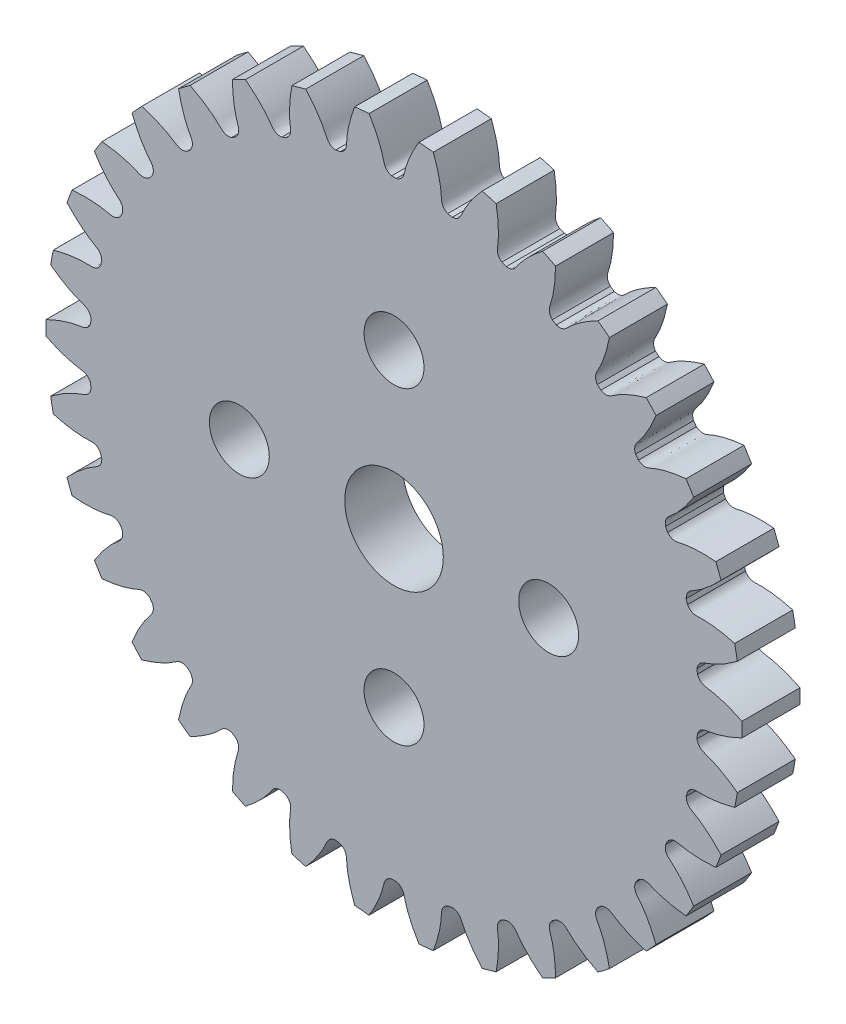
SolidWorks part; units mm, degrees
material "Thornel Mat VMA"
ref_plane "前视基准面" through (0, 0, 0) normal (0, 0, 1) x (1, 0, 0)
ref_plane "上视基准面" through (0, 0, 0) normal (0, 1, 0) x (1, 0, 0)
ref_plane "右视基准面" through (0, 0, 0) normal (1, 0, 0) x (0, 0, -1)
sketch "草图1" plane through (0, 0, 0) normal (0, 0, 1) x (1, 0, 0)
  circle A0 centre (0, 0) radius 18
extrude "凸台-拉伸1" add sketch "草图1" along normal blind 5
ref_axis "基准轴1" through (0, 0, 5) along (0, 0, -1)
sketch "草图2" plane through (0, 0, 0) normal (0, 0, 1) x (1, 0, 0)
  line L0 (0, 0) -> (0, 18) construction
  circle A0 centre (0, 0) radius 18 construction
  arc A1 (0.1221, 15.7495) -> (-0.1221, 15.7495) centre (0, 0) ccw
  arc A2 (3.3716, 20.3699) -> (-3.3716, 20.3699) centre (0, 0) ccw
  spline S0 degree 3 poles (0.1221, 15.7495) (0.4777, 15.8501) (0.5089, 16.1259) (0.5866, 16.4158) (0.6086, 16.4922) (0.6341, 16.5742) (0.6631, 16.6618) (0.6961, 16.7548) (0.7331, 16.8531) (0.7745, 16.9566) (0.8205, 17.0651) (0.8712, 17.1786) (0.9269, 17.2967) (0.9877, 17.4195) (1.054, 17.5467) (1.1259, 17.6781) (1.2035, 17.8136) (1.2872, 17.953) (1.377, 18.0962) (1.4731, 18.2428) (1.5758, 18.3928) (1.6852, 18.5459) (1.8014, 18.7019) (1.9246, 18.8606) (2.055, 19.0217) (2.1928, 19.1851) (2.3379, 19.3506) (2.4907, 19.5178) (2.6512, 19.6865) (2.8195, 19.8566) (3.0576, 20.0877) (3.2437, 20.2577) (3.3716, 20.3699) knots 0 0 0 0 0.130724 0.143504 0.157401 0.172415 0.188546 0.205794 0.224159 0.243641 0.26424 0.285956 0.308788 0.332738 0.357805 0.383988 0.411289 0.439706 0.46924 0.499892 0.53166 0.564545 0.598547 0.633666 0.669902 0.707255 0.745725 0.785312 0.826016 0.867836 0.910774 1 1 1 1
  spline S1 degree 3 poles (-0.1221, 15.7495) (-0.4777, 15.8501) (-0.5089, 16.1259) (-0.5866, 16.4158) (-0.6086, 16.4922) (-0.6341, 16.5742) (-0.6631, 16.6618) (-0.6961, 16.7548) (-0.7331, 16.8531) (-0.7745, 16.9566) (-0.8205, 17.0651) (-0.8712, 17.1786) (-0.9269, 17.2967) (-0.9877, 17.4195) (-1.054, 17.5467) (-1.1259, 17.6781) (-1.2035, 17.8136) (-1.2872, 17.953) (-1.377, 18.0962) (-1.4731, 18.2428) (-1.5758, 18.3928) (-1.6852, 18.5459) (-1.8014, 18.7019) (-1.9246, 18.8606) (-2.055, 19.0217) (-2.1928, 19.1851) (-2.3379, 19.3506) (-2.4907, 19.5178) (-2.6512, 19.6865) (-2.8195, 19.8566) (-3.0576, 20.0877) (-3.2437, 20.2577) (-3.3716, 20.3699) knots 0 0 0 0 0.130724 0.143504 0.157401 0.172415 0.188546 0.205794 0.224159 0.243641 0.26424 0.285956 0.308788 0.332738 0.357805 0.383988 0.411289 0.439706 0.46924 0.499892 0.53166 0.564545 0.598547 0.633666 0.669902 0.707255 0.745725 0.785312 0.826016 0.867836 0.910774 1 1 1 1
extrude "切除-拉伸1" cut sketch "草图2" along normal through all
pattern_circular "阵列(圆周)1" count 34 every 10.588 about axis through (0, 0, 5) along (0, 0, -1) of "切除-拉伸1"
sketch "草图3" plane through (0, 0, 0) normal (0, 0, 1) x (1, 0, 0)
  circle A0 centre (0, 0) radius 17 construction
  dimension "Dn" = 34
ref_plane "基准面1" through (0, 0, 5) normal (0, 0, 1) x (1, 0, 0)
sketch "草图4" plane through (0, 0, 5) normal (0, 0, 1) x (1, 0, 0)
  circle A0 centre (0, 0) radius 2.55
  circle A1 centre (0, 0) radius 8 construction
  circle A2 centre (8, 0) radius 1.55
  circle A3 centre (0, -8) radius 1.55
  circle A4 centre (-8, 0) radius 1.55
  circle A5 centre (0, 8) radius 1.55
  point P15 (0, 0)
  dimension "D1" = 5.1
  dimension "D2" = 16
  dimension "D3" = 3.1
  dimension "D4" = 4
extrude "切除-拉伸2" cut sketch "草图4" against normal blind 10
ref_plane "基准面2" through (0, 0, 5) normal (0, 0, 1) x (1, 0, 0)
sketch "草图5" plane through (0, 0, 5) normal (0, 0, 1) x (1, 0, 0)
  circle A0 centre (-132.5995, 117.3916) radius 416.7363
extrude "切除-拉伸3" cut sketch "草图5" against normal blind 2
